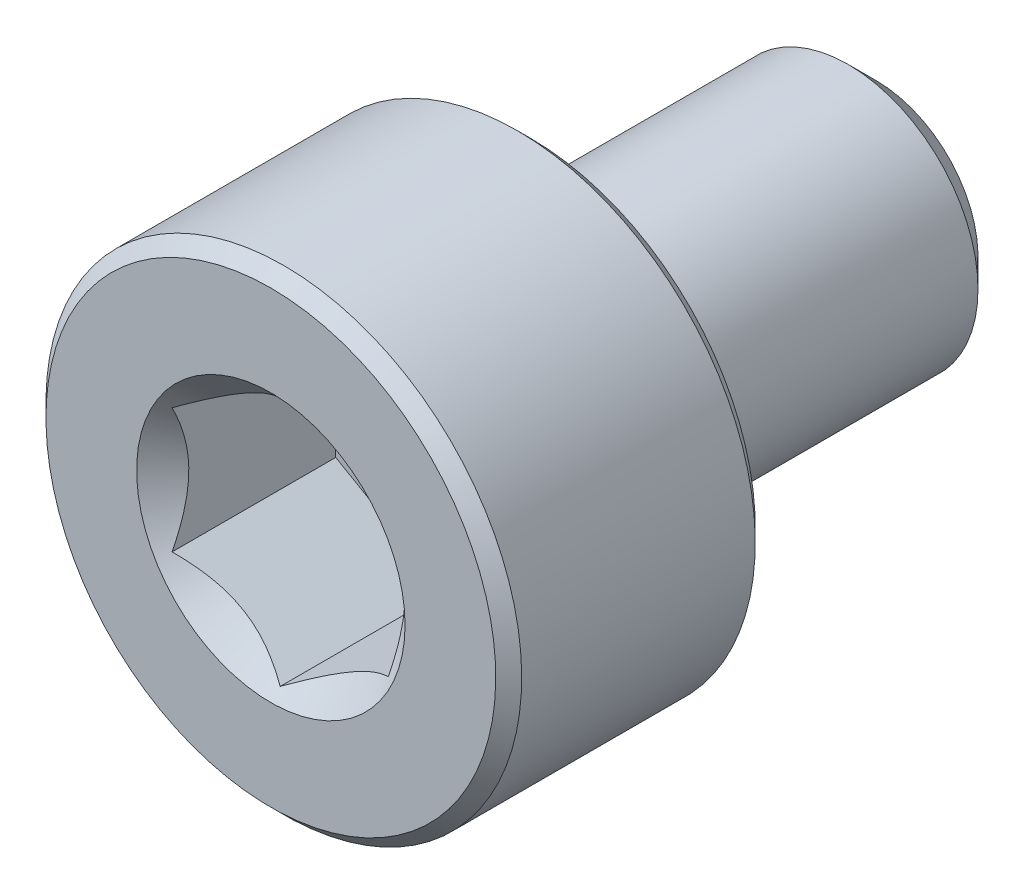
SolidWorks part; units mm, degrees
material "Plain Carbon Steel"
ref_plane "Front Plane" through (0, 0, 0) normal (0, 0, 1) x (1, 0, 0)
ref_plane "Top Plane" through (0, 0, 0) normal (0, 1, 0) x (1, 0, 0)
ref_plane "Right Plane" through (0, 0, 0) normal (1, 0, 0) x (0, 0, -1)
sketch "Sketch1" plane through (0, 0, 0) normal (1, 0, 0) x (0, 0, -1)
  line L0 (-3.5, 0) -> (3.5, 0) construction
  line L1 (3.5, 0) -> (3.5, 1.1752) construction
  line L2 (3.5, 1.1752) -> (3.1752, 1.5) construction
  line L3 (3.1752, 1.5) -> (3.125, 1.5) construction
  line L4 (3.125, 1.5) -> (-0.5, 1.5) construction
  line L5 (-0.5, 1.5) -> (-0.5, 2.75) construction
  line L6 (-0.5, 2.75) -> (-3.5, 2.75) construction
  line L7 (-3.5, 2.75) -> (-3.5, 0) construction
  line L8 (3.5, 1.1752) -> (3.5, 1.5) construction
  line L9 (3.4687, 1.5541) -> (3.7187, 1.1211) construction
  line L10 (3.7187, 1.1211) -> (3.9687, 1.5541) construction
  line L11 (3.9687, 1.5541) -> (3.4687, 1.5541) construction
  line L12 (3.7187, 1.5541) -> (3.7188, 1.5) construction
  line L13 (3.7187, 1.1211) -> (3.7187, 1.1752) construction
  line L14 (3.6875, 1.1752) -> (3.75, 1.1752) construction
  line L15 (3.5, 1.5) -> (3.9375, 1.5) construction
  line L16 (3.4844, 1.5271) -> (3.9531, 1.5271) construction
  line L17 (3.5, 0) -> (3.5, -1.5) construction
  line L18 (-0.65, 2.75) -> (-0.5, 2.6) construction
  line L19 (-3.35, 2.75) -> (-3.5, 2.6) construction
  line L20 (-0.5, 1.5) -> (-0.5, 0) construction
  line L21 (-0.5, 0.75) -> (0.8333, 0.75) construction
  line L22 (0.8333, 0.75) -> (2.1667, 0.75) construction
  line L23 (2.1667, 0.75) -> (3.5, 0.75) construction
  line L24 (0.8333, 0.75) -> (0.8333, 1.5) construction
  line L25 (0.8333, 1.5) -> (0.8333, 2.75) construction
  line L26 (2.1667, 0.75) -> (2.1667, 2.75) construction
  point P0 (-3.5, 1.25)
  point P3 (2.25, 1.5)
  point P4 (0, 0)
  point P18 (2.1667, 1.5)
  point P22 (3.7187, 1.1752)
  point P24 (3.125, 1.5)
  point P25 (3.7188, 1.5)
  point P28 (3.7187, 1.5271)
  point P29 (2.25, -1.5)
  point P30 (0.8333, 1.5)
  point P31 (-2, 2.75)
  point P37 (-1.025, 2.75)
  point P38 (-3.275, 2.75)
  point P45 (0.8333, 0.75)
  point P46 (2.1667, 0.75)
  dimension "D2" = 0.0625
  dimension "D7" = 0.15
  dimension "D8" = 0.15
  dimension "D9" = 0.15
  dimension "D10" = 0.075
  dimension "D11" = 0.375
  dimension "Drive Size" = 2.5
  dimension "Head Diameter" = 5.5
  dimension "Head Height" = 3
  dimension "Thread Pitch" = 0.5
  dimension "Thread Dia" = 3
  dimension "Length" = 4
  dimension "D12" = 0.375
  dimension "D4" = 1.25
  dimension "D3" = 45
sketch "Sketch2" plane through (0, 0, 0) normal (1, 0, 0) x (0, 0, -1)
  line L0 (-3.5, 0) -> (-3.5, 2.6)
  line L1 (-3.35, 2.75) -> (-0.65, 2.75)
  line L2 (-0.5, 2.6) -> (-0.5, 1.65)
  line L4 (3.1752, 1.5) -> (3.5, 1.1752)
  line L5 (3.5, 1.1752) -> (3.5, 0)
  line L6 (-0.5, 2.75) -> (-3.5, 2.75) construction
  line L7 (3.5, 0) -> (-3.5, 0)
  line L8 (-3.35, 2.75) -> (-3.5, 2.6) construction
  line L10 (-3.35, 2.75) -> (-3.5, 2.6)
  line L14 (-0.65, 2.75) -> (-0.5, 2.6) construction
  line L16 (-0.65, 2.75) -> (-0.5, 2.6)
  line L17 (-0.5, 1.5) -> (-0.5, 2.75) construction
  line L19 (-0.35, 1.5) -> (3.1752, 1.5)
  line L20 (3.125, 1.5) -> (-0.5, 1.5) construction
  arc A1 (-0.5, 1.65) -> (-0.35, 1.5) centre (-0.35, 1.65) ccw
  dimension "D3" = 0.15
revolve "Revolve1" add sketch "Sketch2" angle 360 about L7
sketch "Sketch3" plane through (0, 0, 3.5) normal (0, 0, 1) x (1, 0, 0)
  line L1 (1.25, -0.7217) -> (1.25, 0.7217)
  line L2 (1.25, 0.7217) -> (0, 1.4434)
  line L3 (0, 1.4434) -> (-1.25, 0.7217)
  line L4 (-1.25, 0.7217) -> (-1.25, -0.7217)
  line L5 (-1.25, -0.7217) -> (0, -1.4434)
  line L6 (0, -1.4434) -> (1.25, -0.7217)
  circle A0 centre (0, 0) radius 1.25 construction
  circle A1 centre (0, 0) radius 2.75 construction
  circle A2 centre (0, 0) radius 2.75 construction
  circle A3 centre (0, 0) radius 1.4434 construction
  point P13 (0, 0)
  dimension "D1" = 2.8868
extrude "Cut-Extrude1" cut sketch "Sketch3" against normal offset from surface (2 mm away) 1 up to face at (0, 2.6, 0.5)
sketch "Sketch4" plane through (0, 0, 3.5) normal (0, 0, 1) x (1, 0, 0)
  circle A0 centre (0, 0) radius 1.5516
  dimension "D1" = 3.1033
extrude "Cut-Extrude2" cut sketch "Sketch4" against normal up to vertex (1.5 mm away) draft 45 up to point (0, 2.75, 2)
sketch "Sketch11" plane through (0, 0, 0) normal (1, 0, 0) x (0, 0, -1)
  line L0 (-3.5, 0) -> (3.5, 0) construction
  line L1 (-3.5, 0) -> (3.5, 0) construction
  line L2 (0.25, 0) -> (0.25, 1.5) construction
  line L3 (3.125, 1.5) -> (-0.5, 1.5) construction
  line L4 (2.75, 0) -> (2.75, 1.5) construction
  line L6 (3.5, 1.1752) -> (3.5, 1.5) construction
  point P2 (0.25, 0)
  point P3 (2.75, 0)
  dimension "D1" = 0.75
  dimension "D2" = 0.75
sketch "Sketch6" [suppressed] plane through (0, 0, -3.5) normal (0, 0, -1) x (-1, 0, 0)
  circle A0 centre (0, 0) radius 1.5
curve "Helix/Spiral1" [suppressed] pitch 0.5 height 4.5 turns 9
sketch "Sketch10" [suppressed] plane through (0, 0, 0) normal (1, 0, 0) x (0, 0, -1)
  line L0 (-0.35, -2.75) -> (-0.35, 2.75)
  line L5 (-3.5, 0) -> (3.5, 0) construction
  line L6 (-0.35, 1.5) -> (-0.35, -1.5) construction
  point P3 (-0.35, 0)
split "Split1" [suppressed] bodies to split 106
sketch "Sketch7" [suppressed] plane through (0, 0, 0) normal (1, 0, 0) x (0, 0, -1)
  line L0 (3.4844, 1.5271) -> (3.9531, 1.5271)
  line L1 (3.9531, 1.5271) -> (3.75, 1.1752)
  line L2 (3.75, 1.1752) -> (3.6875, 1.1752)
  line L3 (3.6875, 1.1752) -> (3.4844, 1.5271)
sweep "Cut-Sweep1" [suppressed] cut profiles "Sketch7" path "Helix/Spiral1"
sketch "Sketch8" [suppressed] plane through (0, 0, 0) normal (1, 0, 0) x (0, 0, -1)
  line L0 (-0.5, 0) -> (-0.5, 1.5)
  line L1 (-0.35, -1.5) -> (-0.35, 1.5) construction
  line L2 (-0.5, 1.5) -> (-0.35, 1.5)
  line L4 (-0.35, 1.5) -> (0.516, 0)
  line L5 (0.516, 0) -> (-0.5, 0)
  line L6 (3.125, 1.5) -> (-0.5, 1.5) construction
  line L7 (-3.5, 0) -> (3.5, 0) construction
  dimension "D1" = 60
revolve "Revolve2" [suppressed] add sketch "Sketch8" angle 360 about L5
equation "\"D2@Sketch1\" = \"Thread Pitch@Sketch1\" / 8"
equation "\"D4@Helix/Spiral1\" = \"Thread Pitch@Sketch1\""
equation "\"D7@Sketch1\" = \"Head Height@Sketch1\" * .05"
equation "\"D8@Sketch1\"=\"D7@Sketch1\""
equation "\"D9@Sketch1\"=\"D7@Sketch1\""
equation "\"D10@Sketch1\"=\"D7@Sketch1\"/2"
equation "\"D11@Sketch1\"=\"D10@Sketch1\"*5"
equation "\"D4@Sketch1\"=\"Thread Pitch@Sketch1\"*2.5"
equation "\"D12@Sketch1\"=\"Thread Pitch@Sketch1\"*.75"
equation "\"D3@Helix/Spiral1\"=\"Length@Sketch1\"+\"Thread Pitch@Sketch1\""
equation "\"D3@Sketch2\"=\"Thread Dia@Sketch1\"*0.05"
equation "\"D1@Sketch11\"=\"Length@Sketch1\"*0.1875"
equation "\"D2@Sketch11\"=\"D1@Sketch11\""
equation "\"D1@Sketch4\"=\"D1@Sketch3\"*1.075"
